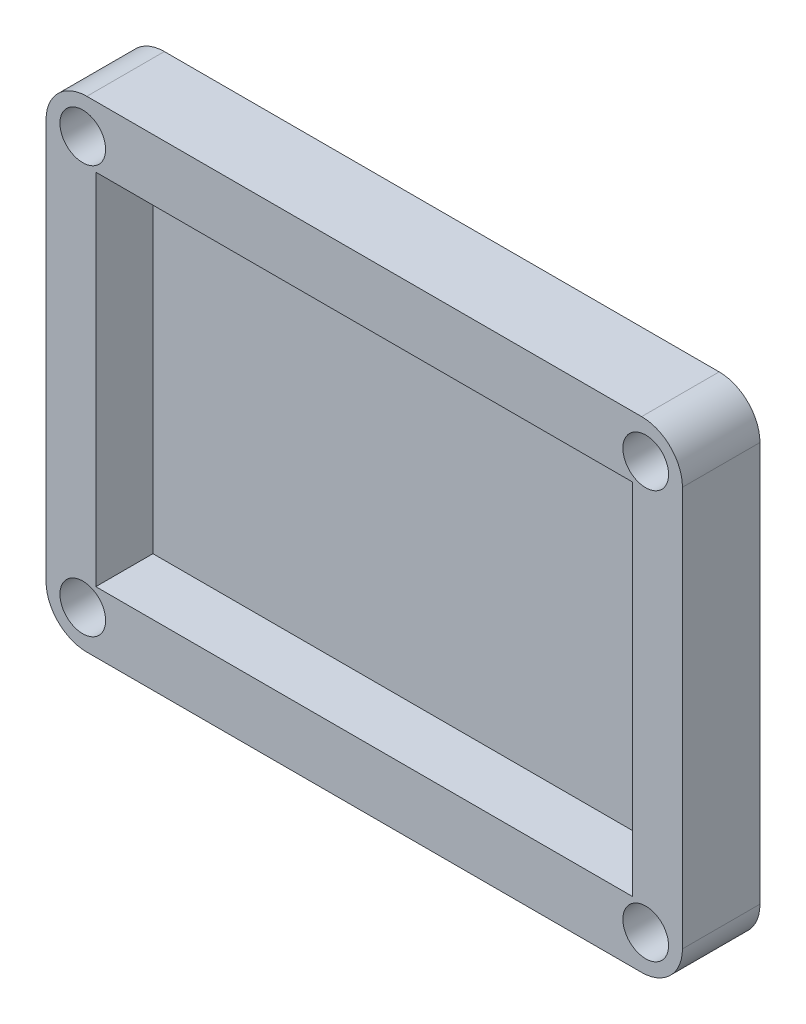
SolidWorks part; units mm, degrees
ref_plane "Front Plane" through (0, 0, 0) normal (1, 0, 0) x (0, 1, 0)
ref_plane "Top Plane" through (0, 0, 0) normal (0, 0, 1) x (0, 1, 0)
ref_plane "Right Plane" through (0, 0, 0) normal (0, 1, 0) x (-1, 0, 0)
sketch "Sketch1" plane through (0, 0, 0) normal (0, 0, 1) x (0, 1, 0)
  line L1 (-27.94, -41.783) -> (27.94, -41.783)
  line L2 (-27.94, -41.783) -> (-27.94, 41.783)
  line L3 (-27.94, 41.783) -> (27.94, 41.783)
  line L4 (27.94, -41.783) -> (27.94, 41.783)
  line L5 (-27.94, -41.783) -> (27.94, 41.783) construction
  line L6 (-27.94, 41.783) -> (27.94, -41.783) construction
  point P0 (0, 0)
  dimension "D1" = 55.88
  dimension "D2" = 83.566
extrude "Boss-Extrude1" add sketch "Sketch1" along normal blind 3.175
sketch "Sketch2" plane through (0, 0, 0) normal (0, 0, 1) x (0, 1, 0)
  line L8 (37.465, -51.308) -> (37.465, 51.308)
  line L9 (37.465, 51.308) -> (-37.465, 51.308)
  line L10 (-37.465, 51.308) -> (-37.465, -51.308)
  line L11 (-37.465, -51.308) -> (37.465, -51.308)
  line L12 (37.465, -51.308) -> (37.465, 51.308)
  line L13 (37.465, 51.308) -> (-37.465, 51.308)
  line L14 (-37.465, 51.308) -> (-37.465, -51.308)
  line L15 (-37.465, -51.308) -> (37.465, -51.308)
  line L16 (27.94, -41.783) -> (27.94, 41.783)
  line L17 (27.94, 41.783) -> (-27.94, 41.783)
  line L18 (-27.94, 41.783) -> (-27.94, -41.783)
  line L19 (-27.94, -41.783) -> (27.94, -41.783)
  line L20 (27.94, -41.783) -> (27.94, 41.783)
  line L21 (27.94, 41.783) -> (-27.94, 41.783)
  line L22 (-27.94, 41.783) -> (-27.94, -41.783)
  line L23 (-27.94, -41.783) -> (27.94, -41.783)
  dimension "D1" = 9.525
  dimension "D2" = 0
extrude "Boss-Extrude2" add sketch "Sketch2" along normal offset from surface (12.065 mm away) 8.89 contours L14 L15 L12 L13 L23 L22 L21 L20 region at (50.0374, 0, 0) up to face at (0, 0, 3.175) offset beyond the face yes
sketch "Sketch3" plane through (0, 0, 12.065) normal (0, 0, 1) x (1, 0, 0)
  line L0 (-43.815, 31.75) -> (43.815, 31.75) construction
  line L1 (-43.815, 31.75) -> (-43.815, -31.75) construction
  circle A0 centre (-43.815, 31.75) radius 3.556
  circle A1 centre (43.815, 31.75) radius 3.556
  circle A2 centre (43.815, -31.75) radius 3.556
  circle A3 centre (-43.815, -31.75) radius 3.556
  point P8 (0, 31.75)
  point P9 (-43.815, 0)
  dimension "D1" = 7.112
  dimension "D2" = 87.63
  dimension "D3" = 63.5
extrude "Cut-Extrude1" cut sketch "Sketch3" against normal through all both and the other way through all
sketch "Sketch4" plane through (0, 0, 12.065) normal (0, 0, 1) x (1, 0, 0)
  line L0 (-51.308, -37.465) -> (51.308, -37.465) construction
  line L1 (-51.308, 37.465) -> (-49.53, 37.465)
  line L2 (-51.308, 37.465) -> (-51.308, -37.465)
  line L3 (-51.308, -37.465) -> (-49.53, -37.465)
  line L4 (-49.53, 37.465) -> (-49.53, -37.465)
  line L5 (-47.371, 31.75) -> (-49.53, 31.75) construction
  line L6 (51.308, 37.465) -> (49.53, 37.465)
  line L7 (51.308, 37.465) -> (51.308, -37.465)
  line L8 (51.308, -37.465) -> (49.53, -37.465)
  line L9 (49.53, 37.465) -> (49.53, -37.465)
  line L10 (-43.815, 35.306) -> (-43.815, 37.465) construction
  line L11 (51.308, 37.465) -> (-51.308, 37.465) construction
  line L12 (-47.371, 31.75) -> (-43.815, 31.75) construction
  line L13 (-43.815, 35.306) -> (-43.815, 31.75) construction
  circle A0 centre (-43.815, 31.75) radius 3.556 construction
extrude "Cut-Extrude2" cut sketch "Sketch4" against normal through all both and the other way through all
fillet "Fillet1" radius 6.35 4 edges at (-49.53, -37.465, 6.0325) (-49.53, 37.465, 6.0325) (49.53, 37.465, 6.0325) (49.53, -37.465, 6.0325)
fillet "Fillet2" radius 0.508 4 edges at (-40.259, 31.75, 0) (47.371, 31.75, 0) (47.371, -31.75, 0) (-40.259, -31.75, 0)
